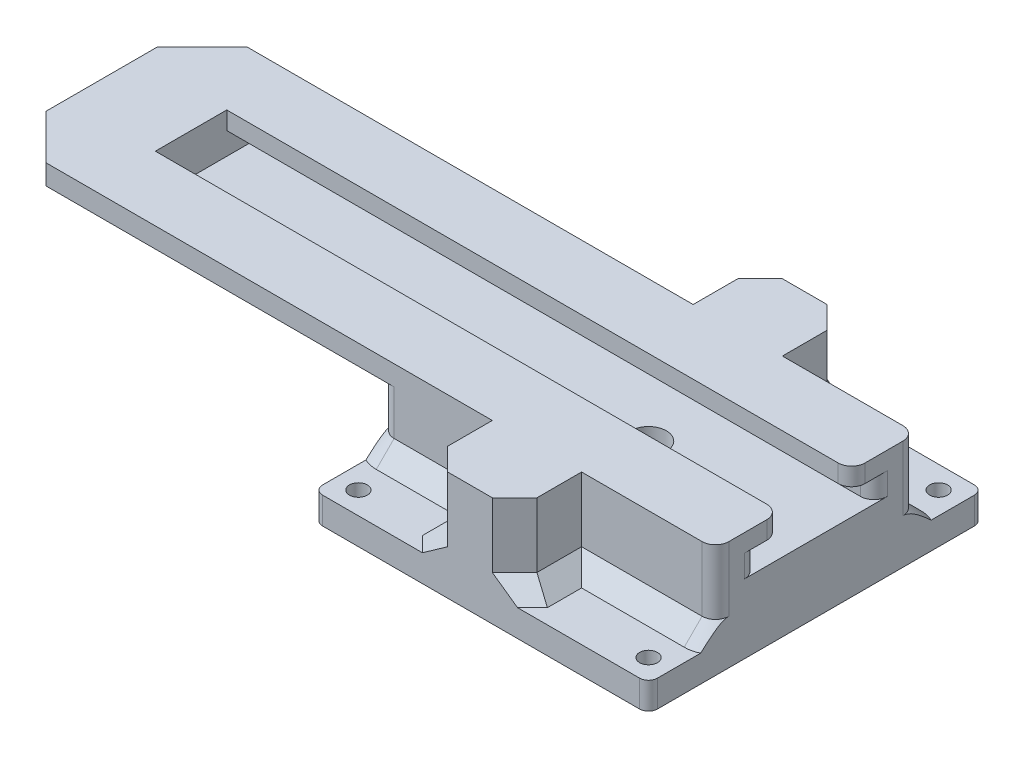
SolidWorks part; units mm, degrees
ref_plane "Front Plane" through (0, 0, 0) normal (0, 0, 1) x (1, 0, 0)
ref_plane "Top Plane" through (0, 0, 0) normal (0, 1, 0) x (1, 0, 0)
ref_plane "Right Plane" through (0, 0, 0) normal (1, 0, 0) x (0, 0, -1)
sketch "Sketch1" plane through (0, 0, 0) normal (0, 1, 0) x (1, 0, 0)
  line L2 (80, -16) -> (220, -16)
  line L3 (220, -16) -> (220, -45.5)
  line L4 (220, -45.5) -> (60, -45.5)
  line L7 (220, 29.5) -> (220, 0)
  line L8 (80, -16) -> (80, 0)
  line L9 (80, 0) -> (220, 0)
  line L10 (220, 29.5) -> (60, 29.5)
  line L11 (60, 29.5) -> (60, -45.5)
  point P2 (80, -8)
  dimension "D1" = 16
  dimension "D2" = 29.5
  dimension "D3" = 29.5
  dimension "D4" = 160
  dimension "D5" = 140
  dimension "D6" = 160
extrude "Boss-Extrude1" add sketch "Sketch1" along normal blind 4
sketch "Sketch2" plane through (0, 0, 0) normal (0, 1, 0) x (1, 0, 0)
  line L0 (209.7303, -8) -> (-59.5425, -8) construction
  line L1 (220, -8) -> (220, 5) construction
  line L4 (220, 5) -> (220, 29.5)
  line L5 (220, 29.5) -> (60, 29.5)
  line L6 (60, 29.5) -> (60, -45.5)
  line L7 (60, 29.5) -> (60, -45.5) construction
  line L8 (220, -21) -> (220, -45.5)
  line L10 (220, -45.5) -> (60, -45.5)
  line L11 (220, 5) -> (80, 5)
  line L12 (80, 5) -> (80, -21)
  line L13 (80, -21) -> (220, -21)
  point P18 (0, -8)
  point P19 (60, -8)
  dimension "D1" = 13
extrude "Boss-Extrude2" add sketch "Sketch2" against normal blind 5
sketch "Sketch3" plane through (0, 0, 0) normal (0, 1, 0) x (1, 0, 0)
  line L0 (60, 29.5) -> (220, 29.5)
  line L1 (220, 29.5) -> (220, -45.5)
  line L2 (220, -45.5) -> (60, -45.5)
  line L3 (60, -45.5) -> (60, 29.5)
extrude "Boss-Extrude3" add sketch "Sketch3" against normal blind 5.5 from offset 5 offset against normal yes
sketch "Sketch4" plane through (0, 0, 0) normal (0, 1, 0) x (1, 0, 0)
  line L6 (60, -8) -> (145, -8) construction
  line L7 (60, -45.5) -> (60, 29.5) construction
  line L8 (145, -8) -> (145, -45.5)
  line L9 (145, -45.5) -> (220, -45.5)
  line L10 (220, -45.5) -> (220, 29.5)
  line L11 (220, 29.5) -> (145, 29.5)
  line L12 (145, 29.5) -> (145, -8)
  line L13 (60, -8) -> (60, 29.5) construction
  dimension "D1" = 85
  dimension "D2" = 37.5
  dimension "D3" = 75
  dimension "D4" = 75
  dimension "D5" = 75
  dimension "D6" = 37.5
extrude "Boss-Extrude4" add sketch "Sketch4" against normal blind 10 from offset 10.5 contours L9 L10 L11 L12 L8 offset against normal yes
sketch "Sketch17" plane through (0, 0, 0) normal (0, 1, 0) x (1, 0, 0)
  line L0 (220, -8) -> (182.5, -8) construction
  line L2 (220, 29.5) -> (220, -45.5) construction
  circle A1 centre (182.5, -8) radius 15
  dimension "D2" = 30
  dimension "D1" = 37.5
extrude "Boss-Extrude7" add sketch "Sketch17" against normal blind 8 from offset 20.5 offset against normal yes
sketch "Sketch5" plane through (0, 0, 0) normal (0, 1, 0) x (1, 0, 0)
  line L0 (180, -45.5) -> (180, 29.5) construction
  line L3 (145, -45.5) -> (220, -45.5) construction
  line L6 (220, 29.5) -> (145, 29.5) construction
  line L9 (145, -8) -> (220, -8) construction
  line L10 (145, 29.5) -> (145, -45.5) construction
  line L11 (220, -45.5) -> (220, 29.5) construction
  circle A1 centre (182.5, -8) radius 10.5
  dimension "D1" = 21
extrude "Cut-Extrude1" cut sketch "Sketch5" along normal blind 3 from offset 28.5 offset against normal yes
sketch "Sketch7" plane through (0, 0, 0) normal (0, 1, 0) x (1, 0, 0)
  circle A1 centre (182.5, -8) radius 2
  dimension "D1" = 4
extrude "Cut-Extrude2" cut sketch "Sketch7" against normal blind 25 from offset 4 offset against normal yes
sketch "Sketch8" plane through (0, 0, 0) normal (0, 1, 0) x (1, 0, 0)
  circle A1 centre (182.5, -8) radius 4
  dimension "D1" = 8
extrude "Cut-Extrude3" cut sketch "Sketch8" against normal blind 18.5 from offset 5 offset against normal yes
sketch "Sketch18" plane through (0, 0, 0) normal (0, 1, 0) x (1, 0, 0)
  line L0 (60, 29.5) -> (170, 29.5)
  line L1 (60, 29.5) -> (220, 29.5) construction
  line L2 (170, 29.5) -> (170, 14.5)
  line L3 (170, 14.5) -> (60, 14.5)
  line L4 (60, -45.5) -> (60, 29.5) construction
  line L5 (60, 14.5) -> (60, 29.5)
  line L6 (60, -8) -> (220, -8) construction
  line L8 (170, -45.5) -> (170, -30.5)
  line L9 (60, -45.5) -> (170, -45.5)
  line L10 (60, -30.5) -> (60, -45.5)
  line L11 (170, -30.5) -> (60, -30.5)
  line L12 (220, 29.5) -> (220, 14.5)
  line L13 (220, 29.5) -> (220, -45.5) construction
  line L14 (220, 14.5) -> (190, 14.5)
  line L15 (190, 14.5) -> (190, 29.5)
  line L16 (190, 29.5) -> (220, 29.5)
  line L17 (220, -45.5) -> (220, -30.5)
  line L18 (220, -30.5) -> (190, -30.5)
  line L19 (190, -45.5) -> (220, -45.5)
  line L20 (190, -30.5) -> (190, -45.5)
  dimension "D1" = 110
  dimension "D2" = 15
  dimension "D3" = 30
  dimension "D4" = 15
extrude "Cut-Extrude5" cut sketch "Sketch18" against normal blind 18.5 from offset 4
sketch "Sketch9" plane through (0, 0, 0) normal (0, 1, 0) x (1, 0, 0)
  line L0 (182.5, -8) -> (150, -8) construction
  line L2 (150, -8) -> (150, -40.5) construction
  line L8 (182.5, -8) -> (182.5, -66.9205) construction
  circle A6 centre (150, -40.5) radius 2
  circle A7 centre (150, 24.5) radius 2
  circle A8 centre (215, 24.5) radius 2
  circle A9 centre (215, -40.5) radius 2
  dimension "D1" = 32.5
  dimension "D2" = 32.5
  dimension "D3" = 4
extrude "Cut-Extrude6" cut sketch "Sketch9" against normal blind 40 from offset 4
chamfer "Chamfer1" distance 10 angle 45 5 edges at (102.5, -10.5, 30.5) (60, -3.25, 30.5) (60, -10.5, 8) (60, -3.25, -14.5) (102.5, -10.5, -14.5)
fillet "Fillet1" radius 2 4 edges at (220, -17.5, 45.5) (145, -17.5, 45.5) (220, -17.5, -29.5) (145, -17.5, -29.5)
chamfer "Chamfer2" distance 5 angle 45 4 edges at (190, -5.25, 45.5) (170, -5.25, 45.5) (170, -5.25, -29.5) (190, -5.25, -29.5)
fillet "Fillet6" radius 3 8 edges at (220, -5.25, 30.5) (220, 2, 16) (220, -5.25, -14.5) (220, 2, 0) (220, -2.5, 21) (220, -2.5, -5) (145, -7.5, -14.5) (145, -7.5, 30.5)
chamfer "Chamfer4" distance 4 angle 45 16 edges at (219.1213, -14.5, -13.6213) (203.5, -14.5, -14.5) (187.5, -14.5, -27) (190, -14.5, -19.5) (172.5, -14.5, -27) (170, -14.5, -19.5) (159, -14.5, -14.5) (159, -14.5, 30.5) (170, -14.5, 35.5) (172.5, -14.5, 43) (187.5, -14.5, 43) (190, -14.5, 35.5) (219.1213, -14.5, 29.6213) (203.5, -14.5, 30.5) (145.8787, -14.5, -13.6213) (145.8787, -14.5, 29.6213)
